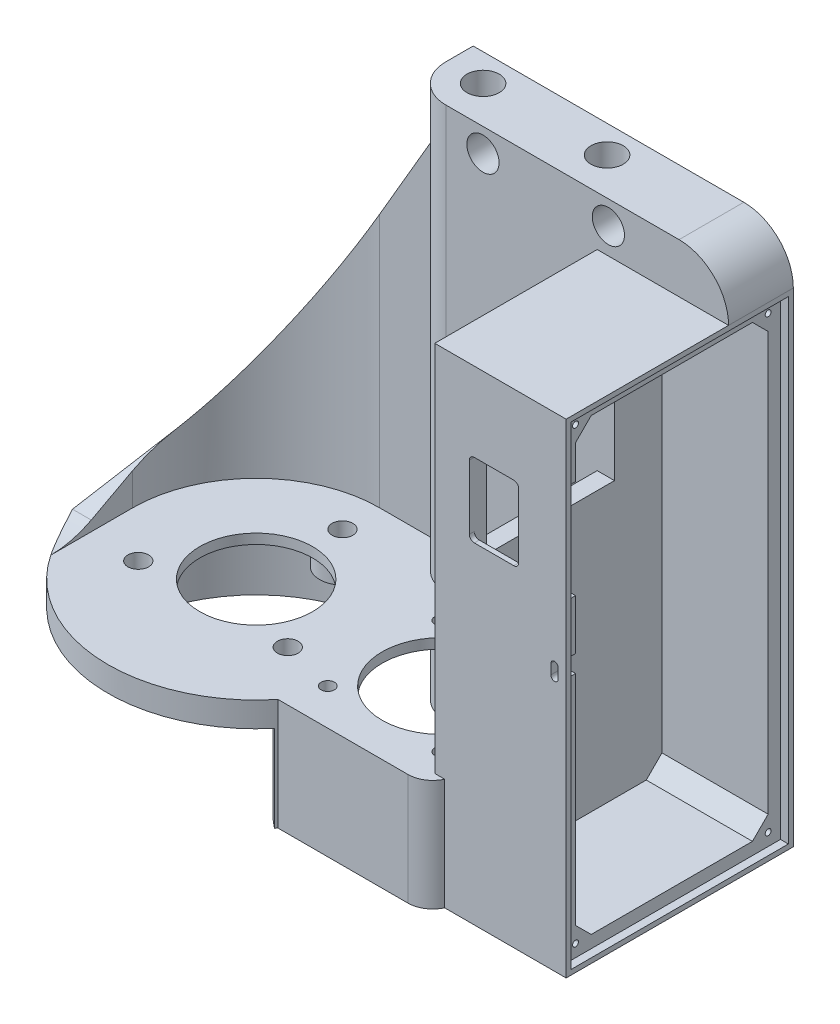
SolidWorks part; units mm, degrees
note: The reader was unsure of these and kept them because the rebuilt part matched: shared geometry of "Sketch1<3>".
ref_plane "Front Plane" through (0, 0, 0) normal (0, 0, 1) x (1, 0, 0)
ref_plane "Top Plane" through (0, 0, 0) normal (0, 1, 0) x (1, 0, 0)
ref_plane "Right Plane" through (0, 0, 0) normal (1, 0, 0) x (0, 0, -1)
sketch "Sketch1" plane through (0, 0, 0) normal (0, 1, 0) x (1, 0, 0)
  line L0 (23.03, 10.795) -> (23.03, -10.795) construction
  line L3 (26.705, -14.47) -> (48.295, -14.47) construction
  line L5 (48.295, 14.47) -> (26.705, 14.47) construction
  line L6 (52.1663, 30) -> (52.1663, -16)
  line L10 (52.1663, -18.8875) -> (23.308, -18.8875)
  line L11 (52.1663, 0) -> (55.6663, 0) construction
  line L12 (37.5, 0) -> (0, 0) construction
  line L19 (55.6663, 26.5) -> (55.6663, -12.5)
  line L20 (0, 0) -> (-21.95, 0) construction
  line L23 (52.1663, 30) -> (77.1663, 30)
  line L24 (55.6663, 26.5) -> (77.1663, 26.5)
  line L28 (55.6663, -12.5) -> (55.6663, -16) construction
  line L29 (77.1663, 30) -> (77.1663, 26.5)
  line L31 (64.6663, 30) -> (64.6663, -16) construction
  line L32 (0, 30) -> (52.1663, 30)
  line L33 (55.6663, -18.8875) -> (55.6663, -16)
  line L34 (55.6663, -16) -> (77.1663, -16)
  line L35 (77.1663, -16) -> (77.1663, -12.5)
  line L36 (77.1663, -12.5) -> (55.6663, -12.5)
  line L40 (52.1663, 16.8875) -> (21.5038, 16.8875) construction
  line L41 (55.6663, -16) -> (52.1663, -16)
  line L42 (51.97, -10.795) -> (51.97, 10.795) construction
  line L43 (77.1663, 26.5) -> (77.1663, -12.5) construction
  line L44 (51.97, 0) -> (52.1663, 0) construction
  line L45 (13.9475, 24.4438) -> (52.1663, 24.4438) construction
  line L46 (37.5, 0) -> (37.5, 14.47) construction
  line L47 (-21.95, 0) -> (-30, 0) construction
  line L48 (52.1663, -18.8875) -> (52.1663, -16) construction
  line L49 (55.6663, -18.8875) -> (52.1663, -18.8875)
  line L50 (37.5, 0) -> (51.97, 0) construction
  line L51 (13.9475, 24.4438) -> (13.9475, 30) construction
  line L52 (0, 0) -> (16.1825, 18.395) construction
  line L53 (16.1825, 18.395) -> (16.5128, 18.7704) construction
  line L54 (16.5128, 18.7704) -> (21.5038, 24.4438) construction
  line L55 (21.5038, 16.8875) -> (21.5038, 30) construction
  line L56 (37.5, -14.47) -> (37.5, -18.8875) construction
  line L57 (37.5, 14.47) -> (37.5, 16.8875) construction
  circle A0 centre (0, 0) radius 21.95 construction
  circle A1 centre (0, 0) radius 11.425
  arc A2 (23.03, 10.795) -> (26.705, 14.47) centre (26.705, 10.795) cw construction
  arc A3 (23.03, -10.795) -> (26.705, -14.47) centre (26.705, -10.795) ccw construction
  arc A4 (48.295, -14.47) -> (51.97, -10.795) centre (48.295, -10.795) ccw construction
  arc A5 (51.97, 10.795) -> (48.295, 14.47) centre (48.295, 10.795) ccw construction
  circle A9 centre (0, 0) radius 24.5 construction
  circle A10 centre (37.5, 0) radius 12
  arc A18 (0, 30) -> (23.308, -18.8875) centre (0, 0) ccw
  arc A19 (21.5038, 16.8875) -> (13.9475, 24.4438) centre (21.5038, 24.4438) cw construction
  dimension "D2" = 22.85
  dimension "D5" = 3.675
  dimension "D7" = 24
  dimension "D1" = 43.9
  dimension "D4" = 30
  dimension "D12" = 49
  dimension "D15" = 7.5563
  dimension "D3" = 3.5
  dimension "D9" = 25
  dimension "D10" = 46
  dimension "D6" = 14.47
  dimension "D8" = 37.5
  dimension "D13" = 38.2188
  dimension "D14" = 0.5
  dimension "D16" = 13.1125
  dimension "D11" = 4.4175
extrude "Boss-Extrude1" add sketch "Sketch1" against normal blind 2
extrude "Boss-Extrude2" add sketch "Sketch1<3>" along normal blind 73.934 and the other way blind 21.066 contours L6 L48 L41 L34 L35 L36 L19 L24 L29 L23 | A0 L3 A4 A5 L5
sketch "Sketch1<3>" plane through (0, 0, 0) normal (0, 1, 0) x (1, 0, 0) same geometry as "Sketch1"
hole_wizard "M5x0.8 Tapped Hole1" positions "Sketch2" profile "Sketch3" tap size "M5x0.8" standard "ANSI Metric" end condition through all
sketch "Sketch2" plane through (0, 0, 0) normal (0, 1, 0) x (1, 0, 0)
  line L0 (-15.1338, -8.7375) -> (15.1338, 8.7375) construction
  line L2 (15.1338, -8.7375) -> (-15.1338, 8.7375) construction
  line L4 (0, 17.475) -> (0, -17.475) construction
  line L6 (0, 17.475) -> (-15.1338, -8.7375) construction
  line L7 (-15.1338, -8.7375) -> (15.1338, -8.7375) construction
  line L8 (15.1338, -8.7375) -> (0, 17.475) construction
  point P0 (0, 17.475)
  point P2 (-15.1338, -8.7375)
  point P4 (15.1338, -8.7375)
  dimension "D1" = 34.95
sketch "Sketch3" plane through (0, 0, -17.475) normal (1, 0, 0) x (0, 0, 1)
  line L0 (0, 0) -> (0, 21.066)
  line L1 (0, 21.066) -> (2.1, 21.066)
  line L2 (2.1, 21.066) -> (2.1, 0)
  line L5 (2.1, 0) -> (0, 0)
  line L11 (0, -6.35) -> (0, 107.95) construction
  dimension "Thru Tap Drill Dia." = 4.2
  dimension "Thru Tap Drill Depth" = 21.066
hole_wizard "M2.5 Clearance Hole1" positions "Sketch4" profile "Sketch5" hole size "M2.5" standard "ANSI Metric" end condition through all
sketch "Sketch4" plane through (0, 0, 0) normal (0, 1, 0) x (1, 0, 0)
  line L0 (26, 11.5) -> (49, 11.5) construction
  line L1 (49, 11.5) -> (49, -11.5) construction
  line L2 (49, -11.5) -> (26, -11.5) construction
  line L3 (26, -11.5) -> (26, 11.5) construction
  line L5 (37.5, 11.5) -> (37.5, -11.5) construction
  circle A5 centre (37.5, 0) radius 12 construction
  point P0 (26, 11.5)
  point P2 (49, 11.5)
  point P4 (49, -11.5)
  point P6 (26, -11.5)
  point P35 (37.5, 0)
  dimension "D1" = 23
sketch "Sketch5" plane through (26, 0, -11.5) normal (1, 0, 0) x (0, 0, 1)
  line L0 (0, 0) -> (0, 21.066)
  line L1 (0, 21.066) -> (1.35, 21.066)
  line L2 (1.35, 21.066) -> (1.35, 0)
  line L5 (1.35, 0) -> (0, 0)
  line L11 (0, -6.35) -> (0, 107.95) construction
  dimension "Thru Hole Dia." = 2.7
  dimension "Thru Hole Depth" = 21.066
sketch "Sketch8" plane through (0, 73.934, 0) normal (0, 1, 0) x (1, 0, 0)
  line L0 (52.1663, 30) -> (52.1663, -16) construction
  line L1 (52.1663, 30) -> (77.1663, 30)
  line L2 (52.1663, 30) -> (52.1663, -16)
  line L3 (52.1663, -16) -> (77.1663, -16)
  line L4 (77.1663, 30) -> (77.1663, -16)
  line L6 (52.1663, -16) -> (77.1663, -16) construction
extrude "Boss-Extrude4" add sketch "Sketch8" against normal blind 2 and the other way blind 1.5
sketch "Sketch9" plane through (0, -21.066, 0) normal (0, -1, 0) x (1, 0, 0)
  line L1 (52.1663, 16) -> (77.1663, 16)
  line L2 (52.1663, 16) -> (52.1663, -30)
  line L3 (52.1663, -30) -> (77.1663, -30)
  line L4 (77.1663, 16) -> (77.1663, -30)
  line L8 (52.1663, 16) -> (77.1663, 16) construction
extrude "Boss-Extrude5" add sketch "Sketch9" against normal blind 2 and the other way blind 1.5
sketch "Sketch65" plane through (55.6663, 0, 0) normal (1, 0, 0) x (0, 0, -1)
  line L0 (-12.5, 71.934) -> (-9.325, 71.934)
  line L1 (-12.5, 71.934) -> (26.5, 71.934) construction
  line L2 (-9.325, 71.934) -> (-12.5, 68.759)
  line L3 (-12.5, -19.066) -> (-12.5, 71.934) construction
  line L4 (-12.5, 68.759) -> (-12.5, 71.934)
  line L5 (26.5, 71.934) -> (23.325, 71.934)
  line L6 (-12.5, 71.934) -> (26.5, 71.934) construction
  line L7 (23.325, 71.934) -> (26.5, 68.759)
  line L8 (26.5, -19.066) -> (26.5, 71.934) construction
  line L9 (26.5, 68.759) -> (26.5, 71.934)
  line L10 (26.5, -15.891) -> (23.325, -19.066)
  line L11 (26.5, -19.066) -> (-12.5, -19.066) construction
  line L12 (23.325, -19.066) -> (26.5, -19.066)
  line L13 (26.5, -19.066) -> (26.5, -15.891)
  line L14 (-9.325, -19.066) -> (-12.5, -15.891)
  line L15 (26.5, -19.066) -> (-12.5, -19.066) construction
  line L16 (-12.5, -15.891) -> (-12.5, -19.066)
  line L17 (-12.5, -19.066) -> (-9.325, -19.066)
  dimension "D1" = 3.175
extrude "Boss-Extrude34" add sketch "Sketch65" along normal up to surface (21.5 mm away) up to face at (77.1663, 26.434, -7)
sketch "Sketch28" plane through (52.1663, 0, 0) normal (-1, 0, 0) x (0, 0, 1)
  line L1 (-18.8875, 62.3215) -> (-30, 62.3215)
  line L3 (-16.8875, 75.434) -> (-30, 75.434)
  line L4 (-30, 62.3215) -> (-30, 75.434)
  line L5 (-30, 0) -> (16, 0) construction
  line L6 (-18.8875, 0) -> (-18.8875, 62.3215)
  line L7 (-18.8875, 0) -> (-16.8875, 0)
  line L9 (-16.8875, 0) -> (-16.8875, 75.434)
  dimension "D1" = 11.1125
  dimension "D2" = 13.1125
  dimension "D3" = 2
extrude "Boss-Extrude17" add sketch "Sketch28" along normal blind 38.2188
sketch "Sketch44" plane through (13.9475, 0, 0) normal (-1, 0, 0) x (0, 0, 1)
  line L0 (-18.8875, 62.3215) -> (-18.8875, 0) construction
  line L1 (-18.8875, 62.3215) -> (-30, 62.3215)
  line L2 (-18.8875, 62.3215) -> (-18.8875, 0)
  line L3 (-18.8875, 0) -> (-30, 0)
  line L4 (-30, 62.3215) -> (-30, 0)
  line L5 (-30, 62.3215) -> (-18.8875, 62.3215) construction
extrude "Boss-Extrude21" add sketch "Sketch44" against normal blind 2
sketch "Sketch46" plane through (0, 0, 0) normal (0, 1, 0) x (1, 0, 0)
  line L0 (15.9475, 30) -> (52.1663, 30) construction
  line L1 (52.1663, 30) -> (15.9475, 30)
  line L5 (15.9475, 30) -> (15.9475, 18.8875)
  line L6 (15.9475, 18.8875) -> (52.1663, 18.8875)
  line L8 (15.9475, 18.8875) -> (52.1663, 18.8875) construction
  line L9 (52.1663, 18.8875) -> (52.1663, 30)
extrude "Cut-Extrude12" cut sketch "Sketch46" against normal through all
sketch "Sketch47" plane through (0, -22.566, 0) normal (0, -1, 0) x (1, 0, 0)
  line L1 (13.9475, -16.8875) -> (52.1663, -16.8875)
  line L2 (13.9475, -16.8875) -> (13.9475, -30)
  line L3 (13.9475, -30) -> (52.1663, -30)
  line L4 (52.1663, -16.8875) -> (52.1663, -30)
extrude "Boss-Extrude23" add sketch "Sketch47" against normal blind 13.1125
sketch "Sketch45" plane through (0, -9.4535, 0) normal (0, 1, 0) x (1, 0, 0)
  line L0 (21.5038, 18.8875) -> (15.9475, 18.8875)
  line L2 (15.9475, 18.8875) -> (15.9475, 24.4437)
  line L5 (52.1663, 18.8875) -> (46.61, 18.8875)
  line L9 (52.1663, 18.8875) -> (52.1663, 24.4438)
  line L10 (52.1663, 30) -> (52.1663, 16.8875) construction
  line L11 (15.9475, 18.8875) -> (52.1663, 18.8875) construction
  line L14 (52.1663, 30) -> (52.1663, 18.8875) construction
  line L15 (15.9475, 30) -> (15.9475, 18.8875) construction
  arc A0 (15.9475, 24.4437) -> (21.5038, 18.8875) centre (21.5038, 24.4437) ccw
  arc A1 (52.1663, 24.4438) -> (46.61, 18.8875) centre (46.61, 24.4438) cw
extrude "Boss-Extrude22" add sketch "Sketch45" along normal up to surface (84.8875 mm away) up to face at (47.76, 75.434, -10.2958)
hole_wizard "1/4 Clearance Hole3" positions "Sketch30" profile "Sketch31" hole size "1/4" standard "ANSI Inch" end condition through all
sketch "Sketch30" plane through (0, 75.434, 0) normal (0, 1, 0) x (1, 0, 0)
  arc A2 (46.61, 18.8875) -> (52.1663, 24.4438) centre (46.61, 24.4438) ccw construction
  arc A3 (15.9475, 24.4437) -> (21.5038, 18.8875) centre (21.5038, 24.4437) ccw construction
  point P0 (46.61, 24.4438)
  point P2 (21.5038, 24.4437)
sketch "Sketch31" plane through (46.61, 75.434, -24.4438) normal (1, 0, 0) x (0, 0, 1)
  line L0 (0, 0) -> (0, 98)
  line L1 (0, 98) -> (3.2639, 98)
  line L2 (3.2639, 98) -> (3.2639, 0)
  line L5 (3.2639, 0) -> (0, 0)
  line L11 (0, -6.35) -> (0, 107.95) construction
  dimension "Thru Hole Dia." = 6.5278
  dimension "Thru Hole Depth" = 98
sketch "Sketch32" plane through (0, 75.434, 0) normal (0, 1, 0) x (1, 0, 0)
  line L0 (21.5038, 16.8875) -> (13.9475, 16.8875)
  line L2 (13.9475, 16.8875) -> (13.9475, 24.4437)
  line L5 (18.2399, 24.4437) -> (13.9475, 24.4437) construction
  line L6 (21.5038, 24.4437) -> (18.2399, 24.4437) construction
  arc A0 (13.9475, 24.4437) -> (21.5038, 16.8875) centre (21.5038, 24.4437) ccw
  circle A1 centre (21.5038, 24.4437) radius 3.2639 construction
extrude "Cut-Extrude5" cut sketch "Sketch32" against normal up to surface (75.434 mm away) up to face at (26, 0, -10.15)
sketch "Sketch48" plane through (0, -22.566, 0) normal (0, -1, 0) x (1, 0, 0)
  line L0 (52.1663, -18.8875) -> (52.1663, -16.8875)
  line L2 (52.1663, -16.8875) -> (13.9475, -16.8875)
  line L3 (13.9475, -16.8875) -> (13.9475, -30)
  line L4 (0, -30) -> (15.9475, -30) construction
  line L5 (13.9475, -30) -> (15.9475, -30)
  line L6 (15.9475, -30) -> (15.9475, -18.8875)
  line L7 (15.9475, -18.8875) -> (52.1663, -18.8875)
  dimension "D1" = 2
extrude "Boss-Extrude24" add sketch "Sketch48" against normal up to surface (20.566 mm away) up to face at (26, -2, -10.15)
sketch "Sketch49" plane through (0, -22.566, 0) normal (0, -1, 0) x (1, 0, 0)
  line L0 (13.9475, -24.4437) -> (13.9475, -16.8875)
  line L2 (13.9475, -16.8875) -> (21.5038, -16.8875)
  arc A0 (13.9475, -24.4437) -> (21.5038, -16.8875) centre (21.5038, -24.4437) cw
  circle A2 centre (21.5038, -24.4437) radius 3.2639 construction
extrude "Cut-Extrude13" cut sketch "Sketch49" against normal up to surface (20.566 mm away) up to face at (26, -2, -10.15)
sketch "Sketch12" plane through (0, 0, -30) normal (0, 0, -1) x (-1, 0, 0)
  line L0 (-13.9475, 75.434) -> (30, 0)
  line L1 (30, 0) -> (-13.9475, 0)
  line L3 (-13.9475, 0) -> (-13.9475, 75.434)
  line L4 (0, 0) -> (-13.9475, 0) construction
  line L5 (30, 0) -> (-23.308, 0) construction
extrude "Boss-Extrude6" add sketch "Sketch12" against normal blind 5
sketch "Sketch14" plane through (0, 0, 0) normal (0, -1, 0) x (1, 0, 0)
  line L0 (-30, -25) -> (-30, -30) construction
  line L2 (-30, 0) -> (-30, -30)
  line L3 (-30, -30) -> (0, -30)
  line L4 (0, 30) -> (-30, 30)
  line L9 (-30, 30) -> (-30, 0)
  arc A0 (-30, 0) -> (0, -30) centre (0, 0) ccw
  arc A2 (23.308, 18.8875) -> (0, -30) centre (0, 0) ccw construction
  arc A7 (0, 30) -> (-30, 0) centre (0, 0) ccw
extrude "Cut-Extrude4" cut sketch "Sketch14" against normal through all contours L2 L3 A0 | L9 A7 L4
sketch "Sketch17" plane through (0, 0, 0) normal (0, 1, 0) x (1, 0, 0)
  line L3 (0, 25) -> (-16.5831, 25)
  line L6 (13.9475, 25) -> (-16.5831, 25) construction
  line L8 (-25, 0) -> (-25, -16.5831)
  arc A0 (0, 25) -> (-25, 0) centre (0, 0) ccw
  arc A1 (-16.5831, 25) -> (23.308, -18.8875) centre (0, 0) ccw construction
  arc A3 (-16.5831, 25) -> (-25, -16.5831) centre (0, 0) ccw
extrude "Boss-Extrude7" add sketch "Sketch17" along normal up to surface (51.4937 mm away) up to face at (2.7358, 56.1896, -27.8057)
sketch "Sketch37" plane through (-25, 0, 0) normal (1, 0, 0) x (0, 0, -1)
  line L0 (-16.5831, 8.5823) -> (-16.5831, 0) construction
  line L1 (-8.3898, 2.0546) -> (7.4416, 10.5274)
  line L3 (-16.5831, 0) -> (-16.5831, 10.5274)
  line L4 (-16.5831, 0) -> (0, 0) construction
  line L5 (-16.5831, 10.5274) -> (7.4416, 10.5274)
  arc A0 (-16.5831, 0) -> (-8.3898, 2.0546) centre (-16.5831, 17.3639) ccw
  ellipse E0 centre (0, 51.4937) end of major axis (0, 102.9874) minor radius 30 (-16.5831, 8.5823) -> (-15.4145, 7.3172) ccw construction
  ellipse E1 centre (0, 51.4937) end of major axis (0, 8.5823) minor radius 25 (0, 8.5823) -> (25, 51.4937) ccw construction
extrude "Cut-Extrude8" cut sketch "Sketch37" against normal through all and the other way up to surface other way up to face at (-15.0888, 12.7972, -15.0888)
hole_wizard "1/4 Clearance Hole2" [suppressed] positions "Sketch24" profile "Sketch25" hole size "1/4" standard "ANSI Inch"
sketch "Sketch24" plane through (0, 0, -16.8875) normal (0, 0, -1) x (-1, 0, 0)
  line L1 (-46.61, 57.675) -> (-46.61, 83.075) construction
  line L4 (-46.61, 57.675) -> (-46.61, 0) construction
  line L11 (-46.61, 83.075) -> (-46.61, 75.434) construction
  line L13 (-49.8739, 75.434) -> (-43.3461, 75.434) construction
  line L14 (-46.61, 57.675) -> (-21.21, 57.675) construction
  line L16 (-21.5038, 0) -> (-52.1663, 0) construction
  point P2 (-46.61, 57.675)
  point P51 (-21.21, 57.675)
  dimension "D1" = 25.4
  dimension "D2" = 57.675
sketch "Sketch25" plane through (46.61, 57.675, -16.8875) normal (1, 0, 0) x (0, -1, 0)
  line L0 (0, 0) -> (0, 13.1125)
  line L1 (0, 13.1125) -> (3.2639, 13.1125)
  line L2 (3.2639, 13.1125) -> (3.2639, 0)
  line L5 (3.2639, 0) -> (0, 0)
  line L11 (0, -6.35) -> (0, 107.95) construction
  dimension "Thru Hole Dia." = 6.5278
  dimension "Thru Hole Depth" = 13.1125
sketch "Sketch57" [suppressed] plane through (0, 0, -30) normal (0, 0, -1) x (-1, 0, 0)
  line L0 (-21.21, 64.6437) -> (-28.4725, 64.6437)
  line L1 (-46.61, 83.075) -> (-46.61, 57.675) construction
  line L2 (-28.4725, 64.6437) -> (-28.4725, 50.7063)
  line L4 (-15.9475, 64.6437) -> (-15.9475, 50.7063)
  line L5 (-52.1663, 89.3375) -> (-39.6413, 89.3375) construction
  line L6 (-52.1663, -16.216) -> (-52.1663, 69.084) construction
  line L7 (-39.6413, 89.3375) -> (-39.6413, 76.8125) construction
  line L8 (-39.6413, 76.8125) -> (-52.1663, 76.8125) construction
  line L9 (-52.1663, 76.8125) -> (-52.1663, 89.3375) construction
  line L10 (-46.61, 83.075) -> (-39.6413, 83.075) construction
  line L11 (-21.21, 64.6437) -> (-21.21, 57.675) construction
  line L12 (-21.21, 57.675) -> (-21.21, 50.7063) construction
  line L13 (-52.1663, 64.6437) -> (-52.1663, 50.7063)
  line L14 (-52.1663, 50.7063) -> (-39.6413, 50.7063)
  line L15 (-39.6413, 50.7063) -> (-39.6413, 64.6437)
  line L16 (-39.6413, 64.6437) -> (-52.1663, 64.6437)
  line L17 (-39.6413, 50.7063) -> (-28.4725, 50.7063) construction
  line L18 (-28.4725, 64.6437) -> (-39.6413, 64.6437) construction
  line L19 (-39.6413, 76.8125) -> (-39.6413, 64.6437) construction
  line L20 (-15.9475, 57.675) -> (-28.4725, 57.675) construction
  line L21 (-15.9475, 50.7063) -> (-28.4725, 50.7063)
  line L22 (-15.9475, 64.6437) -> (-21.21, 64.6437)
  line L23 (-15.9475, 69.084) -> (-15.9475, -16.216) construction
  circle A0 centre (-46.61, 57.675) radius 3.2639
  circle A1 centre (-46.61, 83.075) radius 3.2639 construction
  arc A3 (-46.61, 54.4111) -> (-46.61, 60.9389) centre (-46.61, 57.675) ccw construction
  circle A4 centre (-21.21, 57.675) radius 3.2639
  arc A5 (-21.5038, 60.9257) -> (-21.5038, 54.4243) centre (-21.21, 57.675) ccw construction
  point P38 (-28.4725, 64.6437)
  dimension "D1" = 25.4
  dimension "D2" = 7.2625
extrude "Boss-Extrude29" [suppressed] add sketch "Sketch57" against normal up to surface (11.1125 mm away)
sketch "Sketch60" [suppressed] plane through (0, 0, -16.8875) normal (0, 0, 1) x (1, 0, 0)
  circle A0 centre (21.21, 57.675) radius 4.7625
  arc A2 (21.5038, 54.4243) -> (21.5038, 60.9257) centre (21.21, 57.675) ccw construction
  circle A3 centre (21.21, 57.675) radius 3.2639
  dimension "D1" = 9.525
extrude "Boss-Extrude31" [suppressed] add sketch "Sketch60" against normal up to surface
sketch "Sketch58" plane through (0, 75.434, 0) normal (0, 1, 0) x (1, 0, 0)
  line L0 (13.9475, 24.4437) -> (13.9475, 16.8875)
  line L1 (13.9475, 16.8875) -> (21.5038, 16.8875)
  arc A0 (13.9475, 24.4437) -> (21.5038, 16.8875) centre (21.5038, 24.4437) ccw
  arc A2 (13.9475, 24.4437) -> (21.5038, 16.8875) centre (21.5038, 24.4437) ccw construction
extrude "Cut-Extrude14" [suppressed] cut sketch "Sketch58" against normal up to surface (75.434 mm away)
sketch "Sketch66" [suppressed] plane through (0, 0, -16.8875) normal (0, 0, 1) x (1, 0, 0)
  line L0 (21.21, 57.675) -> (46.61, 57.675) construction
  line L1 (46.61, 57.675) -> (46.61, 83.075) construction
  circle A0 centre (46.61, 83.075) radius 5.5562 construction
  circle A1 centre (46.61, 57.675) radius 5.5562
  circle A2 centre (21.21, 57.675) radius 5.5563
  circle A5 centre (46.61, 57.675) radius 3.2639 construction
  circle A6 centre (21.21, 57.675) radius 3.2639 construction
  dimension "D1" = 11.1125
extrude "Cut-Extrude16" [suppressed] cut sketch "Sketch66" against normal offset from surface (6.7625 mm away) 6.35
sketch "Sketch26" plane through (0, -2, 0) normal (0, -1, 0) x (1, 0, 0)
  line L0 (13.9475, -30) -> (0, -30)
  line L1 (55.6663, 18.8875) -> (23.308, 18.8875) construction
  line L3 (52.1663, 18.8875) -> (54.1663, 18.8875)
  line L5 (54.1663, 18.8875) -> (54.1663, 16)
  line L7 (13.9475, -28) -> (13.9475, -30)
  line L8 (0, -30) -> (13.9475, -30) construction
  line L9 (0, -28) -> (13.9475, -28)
  line L15 (13.9475, -24.4437) -> (13.9475, -30) construction
  line L16 (22.3341, 16.8875) -> (52.1663, 16.8875)
  line L17 (52.1663, -16.8875) -> (52.1663, 16) construction
  line L19 (52.1663, 18.8875) -> (23.308, 18.8875)
  line L20 (54.1663, 16) -> (52.1663, 16)
  line L21 (52.1663, 16) -> (52.1663, 16.8875)
  line L23 (52.1663, 16.8875) -> (52.1663, 18.8875) construction
  arc A2 (22.3341, 16.8875) -> (0, -28) centre (0, 0) ccw
  arc A3 (0, -30) -> (23.308, 18.8875) centre (0, 0) cw
  arc A8 (23.308, 18.8875) -> (0, -30) centre (0, 0) ccw construction
  dimension "D1" = 2
extrude "Boss-Extrude15" add sketch "Sketch26" along normal up to surface (20.566 mm away) up to face at (21.5038, -22.566, -21.1799)
sketch "Sketch41" plane through (52.1663, 0, 0) normal (-1, 0, 0) x (0, 0, 1)
  line L1 (-16.8875, 36.6597) -> (12.5, 36.6597)
  line L2 (-16.8875, 36.6597) -> (-16.8875, 56.6597)
  line L3 (-16.8875, 56.6597) -> (12.5, 56.6597)
  line L4 (12.5, 36.6597) -> (12.5, 56.6597)
  line L5 (12.5, -15.891) -> (12.5, 68.759) construction
  line L9 (-16.8875, 0) -> (-16.8875, 75.434) construction
  line L10 (12.5, 56.6597) -> (-16.8875, 36.6597) construction
  line L12 (-2.1937, 46.6597) -> (-2.1937, -19.066) construction
  line L18 (-23.325, -19.066) -> (9.325, -19.066) construction
  point P5 (0, 0)
  dimension "D1" = 20
  dimension "D2" = 65.7257
extrude "Cut-Extrude10" cut sketch "Sketch41" against normal through all
sketch "Sketch70" plane through (77.1663, 0, 0) normal (1, 0, 0) x (0, 0, -1)
  line L0 (7, 71.934) -> (7, -19.066) construction
  line L1 (-12.5, 71.934) -> (26.5, 71.934) construction
  line L2 (-12.5, 71.934) -> (-12.5, -19.066) construction
  line L3 (-12.5, -19.066) -> (26.5, -19.066) construction
  line L4 (26.5, 71.934) -> (26.5, -19.066) construction
  line L5 (-12.5, 26.434) -> (26.5, 26.434) construction
  line L6 (-12.5, -15.891) -> (-12.5, 68.759) construction
  line L7 (26.5, -15.891) -> (26.5, 68.759) construction
  circle A0 centre (-12.5, 71.934) radius 0.595
  circle A1 centre (26.5, 71.934) radius 0.595
  circle A2 centre (26.5, -19.066) radius 0.595
  circle A3 centre (-12.5, -19.066) radius 0.595
  point P16 (7, 26.434)
  dimension "D1" = 1.19
  dimension "D2" = 39
  dimension "D3" = 91
extrude "Cut-Extrude17" cut sketch "Sketch70" against normal blind 10
sketch "Sketch71" plane through (0, 0, 16) normal (0, 0, 1) x (1, 0, 0)
  line L1 (60.1663, 59.434) -> (68.1663, 59.434)
  line L2 (59.1663, 58.434) -> (59.1663, 45.434)
  line L3 (60.1663, 44.434) -> (68.1663, 44.434)
  line L4 (69.1663, 58.434) -> (69.1663, 45.434)
  line L5 (77.1663, -22.566) -> (77.1663, 75.434) construction
  line L6 (75.6663, 31.034) -> (75.6663, 29.034)
  line L8 (77.1663, 29.034) -> (77.1663, 31.034)
  line L9 (75.6663, 30.034) -> (77.1663, 30.034) construction
  line L10 (75.6663, 30.034) -> (75.6663, -22.566) construction
  line L12 (69.1663, 59.434) -> (59.1663, 44.434) construction
  line L13 (77.1663, 51.934) -> (64.1663, 51.934) construction
  line L14 (64.1663, 51.934) -> (64.1663, -22.566) construction
  line L16 (77.1663, -22.566) -> (54.1663, -22.566) construction
  arc A0 (77.1663, 31.034) -> (75.6663, 31.034) centre (76.4163, 31.034) ccw
  arc A1 (75.6663, 29.034) -> (77.1663, 29.034) centre (76.4163, 29.034) ccw
  arc A2 (60.1663, 59.434) -> (59.1663, 58.434) centre (60.1663, 58.434) ccw
  arc A3 (68.1663, 59.434) -> (69.1663, 58.434) centre (68.1663, 58.434) cw
  arc A4 (68.1663, 44.434) -> (69.1663, 45.434) centre (68.1663, 45.434) ccw
  arc A5 (59.1663, 45.434) -> (60.1663, 44.434) centre (60.1663, 45.434) ccw
  point P29 (59.1663, 59.434)
  point P35 (69.1663, 44.434)
  dimension "D9" = 1
  dimension "D1" = 2
  dimension "D3" = 1.5
  dimension "D4" = 52.6
  dimension "D5" = 15
  dimension "D6" = 10
  dimension "D7" = 74.5
  dimension "D8" = 13
extrude "Cut-Extrude19" cut sketch "Sketch71" against normal up to surface (3.5 mm away) up to face at (60.1663, 36.5469, 12.5)
sketch "Sketch72" plane through (0, 0, 0) normal (-1, 0, 0) x (0, 0, 1)
  line L1 (30, -5.04) -> (28, -5.04)
  line L2 (30, -5.04) -> (30, -22.566)
  line L3 (30, -22.566) -> (28, -22.566)
  line L4 (28, -5.04) -> (28, -22.566)
  line L7 (28, -5.04) -> (28, -2) construction
  line L8 (-11.425, -2) -> (11.425, -2) construction
  line L9 (30, -22.566) -> (30, 0) construction
  dimension "D1" = 2
  dimension "D3" = 3.04
revolve "Cut-Revolve1" cut sketch "Sketch72" angle 50 about axis through (0, -125.9293, 0) along (0, 1, 0)
sketch "Sketch73" plane through (0, -2, 0) normal (0, -1, 0) x (1, 0, 0)
  circle A0 centre (-15.1338, 8.7375) radius 2.1
  circle A1 centre (15.1338, 8.7375) radius 2.1
  circle A2 centre (0, -17.475) radius 2.1
  circle A3 centre (0, -17.475) radius 2.1 construction
  circle A4 centre (15.1338, 8.7375) radius 2.1 construction
  circle A5 centre (-15.1338, 8.7375) radius 2.1 construction
  circle A6 centre (-15.1338, 8.7375) radius 4.6
  circle A7 centre (15.1338, 8.7375) radius 4.6
  circle A8 centre (0, -17.475) radius 4.6
  dimension "D1" = 2.5
extrude "Boss-Extrude37" add sketch "Sketch73" along normal offset from surface (4.54 mm away) 6.54 up to face at (26, 0, -10.15)
sketch "Sketch76" plane through (77.1663, 0, 0) normal (1, 0, 0) x (0, 0, -1)
  line L0 (-12.5, 31.034) -> (-12.5, 68.759) construction
  line L1 (-12.5, 61.934) -> (-15, 61.934)
  line L2 (-12.5, 61.934) -> (-12.5, 41.934)
  line L3 (-12.5, 41.934) -> (-15, 41.934)
  line L4 (-15, 61.934) -> (-15, 41.934)
  line L5 (-12.5, 45.434) -> (-12.5, 58.434) construction
  line L6 (-12.5, 51.934) -> (-15, 51.934) construction
  line L7 (-15, 51.934) -> (-16, 51.934) construction
  line L10 (-16, 31.034) -> (-16, 75.434) construction
  point P6 (-12.5, 51.934)
  dimension "D1" = 20
  dimension "D2" = 1
extrude "Cut-Extrude20" cut sketch "Sketch76" against normal up to surface (18 mm away) up to face at (59.1663, 51.934, 14.25)
sketch "Sketch78" plane through (77.1663, 0, 0) normal (1, 0, 0) x (0, 0, -1)
  line L0 (7, -21.566) -> (7, -22.566) construction
  line L1 (-16, 75.434) -> (30, 75.434)
  line L2 (-16, 75.434) -> (-16, -22.566)
  line L3 (-16, -22.566) -> (30, -22.566)
  line L4 (30, 75.434) -> (30, -22.566)
  line L5 (-15, 74.434) -> (29, 74.434)
  line L6 (-15, 74.434) -> (-15, -21.566)
  line L7 (-15, -21.566) -> (29, -21.566)
  line L8 (29, 74.434) -> (29, -21.566)
  line L9 (7, 75.434) -> (7, 74.434) construction
  line L10 (29, 26.434) -> (30, 26.434) construction
  dimension "D1" = 1
extrude "Boss-Extrude38" add sketch "Sketch78" along normal blind 1.6
sketch "Sketch81" plane through (77.1663, 0, 0) normal (1, 0, 0) x (0, 0, -1)
  line L1 (-14.25, 61.934) -> (-15, 61.934)
  line L2 (-14.25, 61.934) -> (-14.25, 41.934)
  line L3 (-14.25, 41.934) -> (-15, 41.934)
  line L4 (-15, 61.934) -> (-15, 41.934)
  line L6 (-15, 41.934) -> (-12.5, 41.934) construction
  line L7 (-15, 74.434) -> (-15, -21.566) construction
  line L8 (-15, 74.434) -> (-15, 61.934) construction
  line L9 (-12.5, 61.934) -> (-15, 61.934) construction
  dimension "D1" = 0.75
extrude "Boss-Extrude41" add sketch "Sketch81" against normal blind 1
sketch "Sketch82" plane through (0, 0, 12.5) normal (0, 0, -1) x (-1, 0, 0)
  line L0 (-76.4163, 31.784) -> (-77.1663, 31.784)
  line L1 (-77.1663, 31.034) -> (-77.1663, 41.934) construction
  line L2 (-77.1663, 31.784) -> (-77.1663, 28.284)
  line L3 (-77.1663, -15.891) -> (-77.1663, 29.034) construction
  line L4 (-77.1663, 28.284) -> (-76.4163, 28.284)
  line L5 (-76.4163, 31.784) -> (-76.4163, 28.284)
  arc A0 (-75.6663, 31.034) -> (-77.1663, 31.034) centre (-76.4163, 31.034) ccw construction
  arc A1 (-77.1663, 29.034) -> (-75.6663, 29.034) centre (-76.4163, 29.034) ccw construction
extrude "Cut-Extrude22" cut sketch "Sketch82" against normal up to surface (2.5 mm away) up to face at (77.6996, 27.634, 15)
sketch "Sketch80" plane through (52.1663, 0, 0) normal (-1, 0, 0) x (0, 0, 1)
  line L0 (-16.8875, 75.434) -> (16, 75.434)
  line L1 (16, 75.434) -> (16, 0)
  line L2 (16, 0) -> (15, 0)
  line L3 (-16.8875, 0) -> (16, 0) construction
  line L4 (15, 0) -> (15, 74.434)
  line L5 (15, 74.434) -> (-16.8875, 74.434)
  line L6 (-16.8875, 56.6597) -> (-16.8875, 75.434) construction
  line L7 (-16.8875, 74.434) -> (-16.8875, 75.434)
  dimension "D1" = 1
extrude "Boss-Extrude39" [suppressed] add sketch "Sketch80" along normal blind 28.7663
sketch "Sketch83" [suppressed] plane through (23.4, 0, 0) normal (-1, 0, 0) x (0, 0, 1)
  line L0 (-16.8875, 75.434) -> (-16.8875, 74.434) construction
  line L1 (-16.8875, 75.434) -> (16, 75.434)
  line L2 (-16.8875, 75.434) -> (-16.8875, 0)
  line L3 (-16.8875, 0) -> (16, 0)
  line L4 (16, 75.434) -> (16, 0)
  line L5 (16, 75.434) -> (-16.8875, 75.434) construction
  line L6 (16, 0) -> (16, 75.434) construction
extrude "Boss-Extrude42" [suppressed] add sketch "Sketch83" along normal blind 1
sketch "Sketch84" plane through (0, -2, 0) normal (0, -1, 0) x (1, 0, 0)
  line L0 (55.6663, 18.8875) -> (54.1663, 18.8875) construction
  line L1 (55.6663, 18.8875) -> (54.1663, 18.8875)
  line L2 (55.6663, 18.8875) -> (55.6663, 16)
  line L3 (55.6663, 16) -> (54.1663, 16)
  line L4 (54.1663, 18.8875) -> (54.1663, 16)
extrude "Cut-Extrude23" cut sketch "Sketch84" against normal up to surface (2 mm away) up to face at (26, 0, -10.15)
sketch "Sketch85" plane through (0, 75.434, 0) normal (0, 1, 0) x (1, 0, 0)
  line L0 (13.9475, 30) -> (78.7663, 30)
  line L1 (78.7663, 30) -> (13.9475, 30) construction
  line L2 (78.7663, 30) -> (78.7663, 16.8875)
  line L3 (78.7663, 16.8875) -> (21.5038, 16.8875)
  line L4 (13.9475, 24.4437) -> (13.9475, 30)
  line L5 (24.7677, 24.4437) -> (25.7677, 24.4437) construction
  line L6 (24.7677, 24.4437) -> (21.5038, 24.4437) construction
  line L7 (29.0316, 24.4437) -> (54.4316, 24.4437) construction
  line L8 (54.4316, 24.4437) -> (54.4316, 30) construction
  line L9 (54.4316, 24.4437) -> (78.7663, 24.4437) construction
  line L10 (78.7663, 30) -> (78.7663, -16) construction
  arc A0 (21.5038, 16.8875) -> (13.9475, 24.4437) centre (21.5038, 24.4437) cw
  circle A1 centre (29.0316, 24.4437) radius 3.2639 construction
  circle A3 centre (21.5038, 24.4437) radius 3.2639 construction
  arc A4 (13.9475, 24.4437) -> (21.5038, 16.8875) centre (21.5038, 24.4437) ccw construction
  circle A5 centre (54.4316, 24.4437) radius 3.2639 construction
  circle A6 centre (21.5038, 24.4437) radius 3.2639
  circle A7 centre (46.61, 24.4438) radius 3.2639
  circle A8 centre (46.61, 24.4438) radius 3.2639 construction
  point P26 (78.7663, 30)
  point P31 (78.7663, 16.8875)
  dimension "D1" = 1
  dimension "D2" = 25.4
extrude "Boss-Extrude43" add sketch "Sketch85" along normal blind 10.025
hole_wizard "1/4 Clearance Hole4" positions "Sketch86" profile "Sketch87" hole size "1/4" standard "ANSI Inch" end condition through all
sketch "Sketch86" plane through (0, 0, -16.8875) normal (0, 0, 1) x (1, 0, 0)
  line L0 (29.0316, 80.6965) -> (29.0316, 75.434) construction
  line L2 (54.4316, 80.6965) -> (54.4316, 75.434) construction
  line L6 (25.7677, 75.434) -> (32.2955, 75.434) construction
  line L8 (32.2955, 75.434) -> (25.7677, 75.434) construction
  line L10 (52.1663, 75.434) -> (78.7663, 75.434) construction
  line L11 (32.2955, 75.434) -> (32.2955, 80.6965) construction
  line L14 (29.0316, 80.6965) -> (29.0316, 85.459) construction
  line L15 (21.5038, 85.459) -> (78.7663, 85.459) construction
  line L17 (32.2955, 80.6965) -> (54.4316, 80.6965) construction
  circle A0 centre (29.0316, 80.6965) radius 3.2639 construction
  circle A1 centre (54.4316, 80.6965) radius 3.2639 construction
  point P0 (29.0316, 80.6965)
  point P2 (54.4316, 80.6965)
  dimension "D1" = 4.7625
sketch "Sketch87" plane through (29.0316, 80.6965, -16.8875) normal (1, 0, 0) x (0, -1, 0)
  line L0 (0, 0) -> (0, 13.1125)
  line L1 (0, 13.1125) -> (3.2639, 13.1125)
  line L2 (3.2639, 13.1125) -> (3.2639, 0)
  line L5 (3.2639, 0) -> (0, 0)
  line L11 (0, -6.35) -> (0, 107.95) construction
  dimension "Thru Hole Dia." = 6.5278
  dimension "Thru Hole Depth" = 13.1125
sketch "Sketch89" plane through (0, 62.3215, 0) normal (0, -1, 0) x (1, 0, 0)
  line L0 (15.9475, -30) -> (15.9475, -24.4437)
  line L1 (21.5038, -18.8875) -> (46.61, -18.8875)
  line L2 (52.1663, -24.4438) -> (52.1663, -30)
  line L3 (52.1663, -30) -> (15.9475, -30)
  arc A0 (15.9475, -24.4437) -> (21.5038, -18.8875) centre (21.5038, -24.4438) cw
  arc A1 (21.5038, -18.8875) -> (15.9475, -24.4437) centre (21.5038, -24.4437) ccw construction
  arc A2 (46.61, -18.8875) -> (52.1663, -24.4438) centre (46.61, -24.4438) cw
  circle A3 centre (21.5038, -24.4437) radius 3.2639
  circle A4 centre (46.61, -24.4438) radius 3.2639
  circle A5 centre (21.5038, -24.4437) radius 3.2639 construction
  circle A6 centre (46.61, -24.4438) radius 3.2639 construction
extrude "Cut-Extrude24" cut sketch "Sketch89" against normal offset from surface (10.025 mm away) 13.1125 up to face at (41.0733, 85.459, -23.3308)
fillet "Fillet1" radius 3 2 edges at (52.1663, -12.283, -16.8875) (52.1663, -12.283, 16.8875)
fillet "Fillet2" radius 5 1 edges at (54.1663, -11.283, 18.8875)
sketch "Sketch90" plane through (0, 0, -16.8875) normal (0, 0, 1) x (1, 0, 0)
  line L0 (78.7663, 75.434) -> (78.7663, 85.459)
  line L1 (78.7663, 85.459) -> (78.7663, 75.434) construction
  line L2 (21.5038, 85.459) -> (78.7663, 85.459) construction
  line L3 (78.7663, 85.459) -> (68.7413, 85.459)
  arc A0 (68.7413, 85.459) -> (78.7663, 75.434) centre (68.7413, 75.434) cw
  point P8 (0, 0)
  point P9 (0, 0)
  point P10 (78.7663, 76.9515)
extrude "Cut-Extrude25" cut sketch "Sketch90" against normal through all
equation "\"mc\"= 0.5'minimum clearance"
equation "\"D2@Sketch1\"=\"chd\"+2*\"mc\""
equation "\"chd\"= 21.85000000'commutator hub diameter"
equation "\"cfd\"= 43.90000000'commutator flange diameter"
equation "\"D1@Boss-Extrude1\"=\"mint\""
equation "\"mint\"= 2'minimum thickness"
equation "\"D7@Sketch1\"=23mm+2*\"mc\""
equation "\"D1@Sketch1\"=\"cfd\""
